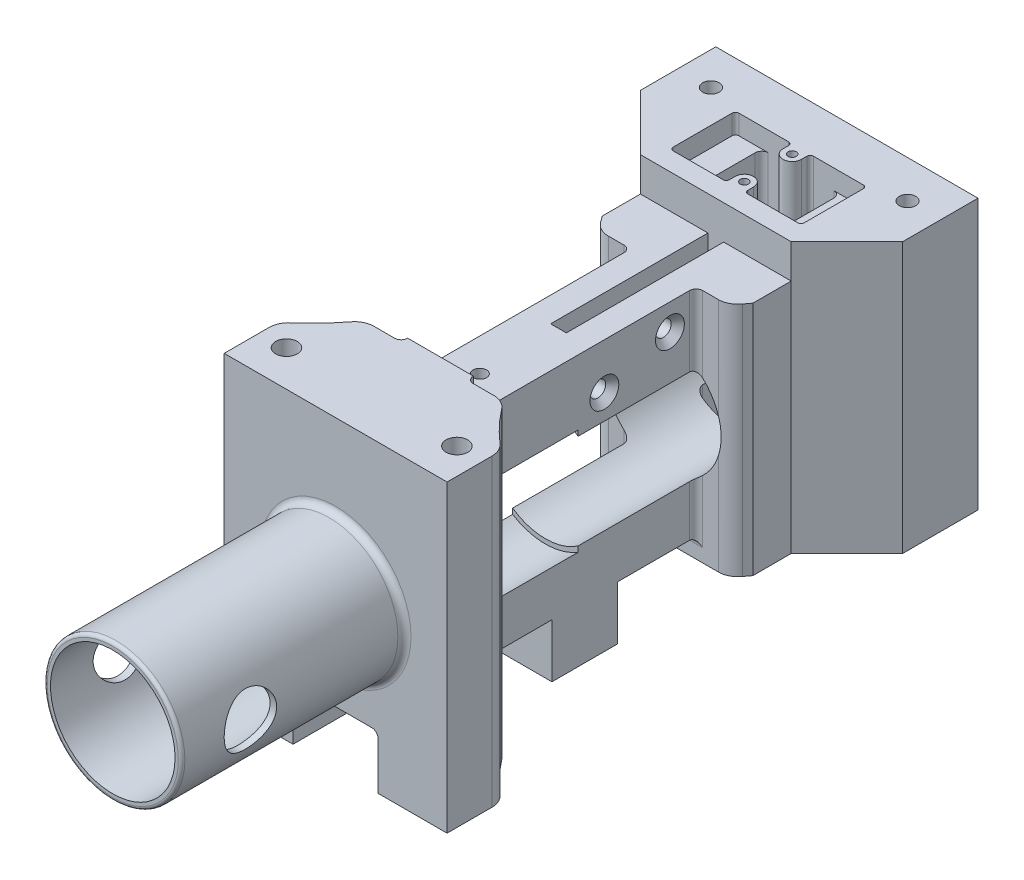
SolidWorks part; units mm, degrees
material "6061 合金"
ref_plane "前视基准面" through (0, 0, 0) normal (0, 0, 1) x (1, 0, 0)
ref_plane "上视基准面" through (0, 0, 0) normal (0, 1, 0) x (1, 0, 0)
ref_plane "右视基准面" through (0, 0, 0) normal (1, 0, 0) x (0, 0, -1)
sketch "草图1" plane through (0, 0, 0) normal (0, 0, 1) x (1, 0, 0)
  line L1 (-20, 18) -> (20, 18)
  line L2 (-20, 18) -> (-20, -18)
  line L3 (-20, -18) -> (20, -18)
  line L4 (20, 18) -> (20, -18)
  line L5 (-20, 18) -> (20, -18) construction
  line L6 (-20, -18) -> (20, 18) construction
  circle A0 centre (0, 0) radius 8.8
  point P0 (0, 0)
  dimension "D1" = 36
  dimension "D3" = 17.6
  dimension "D2" = 40
extrude "凸台-拉伸1" add sketch "草图1" along normal blind 65
sketch "草图2" plane through (0, 0, 0) normal (0, 1, 0) x (1, 0, 0)
  line L0 (0, 0) -> (0, -32) construction
  line L1 (-36.5, -32) -> (36.5, -32) construction
  circle A0 centre (-36.5, -32) radius 31.5
  circle A1 centre (36.5, -32) radius 31.5
  point P6 (0, -32)
  dimension "D1" = 32
  dimension "D3" = 63
  dimension "D2" = 73
extrude "切除-拉伸1" cut sketch "草图2" against normal through all both and the other way through all
ref_plane "基准面1" through (0, 0, 65) normal (0, 0, 1) x (1, 0, 0)
sketch "草图3" plane through (0, 0, 65) normal (0, 0, 1) x (1, 0, 0)
  circle A0 centre (0, 0) radius 9.5
  dimension "D1" = 19
extrude "切除-拉伸2" cut sketch "草图3" against normal blind 32
sketch "草图4" plane through (0, 0, 65) normal (0, 0, 1) x (1, 0, 0)
  circle A0 centre (0, 0) radius 10.5
  circle A1 centre (0, 0) radius 9.5
  dimension "D1" = 19
  dimension "D2" = 21
extrude "凸台-拉伸2" add sketch "草图4" along normal blind 34
sketch "草图5" plane through (0, 0, 0) normal (1, 0, 0) x (0, 0, -1)
  line L0 (0, 0) -> (-65, 0) construction
  line L1 (-65, 19.8) -> (-65, -19.8) construction
  line L2 (-65, 0) -> (-88.5, 0) construction
  circle A0 centre (-88.5, 0) radius 4
  dimension "D2" = 8
  dimension "D1" = 23.5
extrude "切除-拉伸3" cut sketch "草图5" against normal through all both and the other way through all
sketch "草图6" plane through (0, 0, 0) normal (0, 1, 0) x (1, 0, 0)
  line L0 (-1.2, 0) -> (1.2, 0)
  line L1 (20, 0) -> (-20, 0) construction
  line L2 (1.2, 0) -> (1.2, -31)
  line L3 (1.2, -31) -> (-1.2, -31)
  line L4 (-1.2, -31) -> (-1.2, 0)
  point P6 (0, 0)
  dimension "D1" = 2.4
  dimension "D2" = 31
extrude "切除-拉伸4" cut sketch "草图6" along normal through all
sketch "草图7" plane through (0, 0, 0) normal (1, 0, 0) x (0, 0, -1)
  line L0 (0, 0) -> (-44.3363, 0) construction
  line L1 (0, -18) -> (0, 18) construction
  circle A0 centre (-19, 14) radius 0.75
  circle A1 centre (-29, 11) radius 0.75
  dimension "D1" = 14
  dimension "D3" = 1.5
  dimension "D4" = 10
  dimension "D6" = 1.5
  dimension "D2" = 14
  dimension "D5" = 3
extrude "切除-拉伸5" cut sketch "草图7" against normal through all both and the other way through all
fillet "圆角1" radius 1 1 edges at (10.5, 0, 65)
fillet "圆角2" radius 0.5 1 edges at (10.5, 0, 99)
sketch "草图8" plane through (0, 0, 0) normal (0, 0, 1) x (1, 0, 0)
  line L1 (20, -18) -> (-20, -18)
  line L2 (20, -18) -> (20, 18)
  line L3 (20, 18) -> (-20, 18)
  line L4 (-20, -18) -> (-20, 18)
  line L5 (20, -18) -> (-20, 18) construction
  line L6 (20, 18) -> (-20, -18) construction
  point P0 (0, 0)
extrude "切除-拉伸6" cut sketch "草图8" along normal blind 7
ref_plane "基准面2" through (0, -18, 0) normal (0, -1, 0) x (-1, 0, 0)
sketch "草图10" plane through (0, -18, 0) normal (0, -1, 0) x (-1, 0, 0)
  line L0 (-20, -65) -> (20, -65)
  line L1 (20, -65) -> (20, -50)
  line L2 (20, -50) -> (-20, -50)
  line L3 (-20, -50) -> (-20, -65)
  line L4 (-17.3362, -7) -> (17.3362, -7)
  line L5 (17.3362, -7) -> (17.3362, -15)
  line L6 (17.3362, -15) -> (-17.3362, -15)
  line L7 (-17.3362, -15) -> (-17.3362, -7)
  dimension "D1" = 15
  dimension "D2" = 8
extrude "凸台-拉伸3" add sketch "草图10" along normal blind 6.1
sketch "草图17" plane through (0, 0, 0) normal (0, 1, 0) x (1, 0, 0)
  line L0 (0, 0) -> (0, -7) construction
  line L1 (0, -7) -> (-11.5, -7) construction
  line L2 (-11.5, -7) -> (-11.5, -15)
  line L3 (-11.5, -15) -> (-5, -15)
  line L4 (-5, -15) -> (-5, -50)
  line L5 (-5, -50) -> (-17, -50)
  line L6 (-17, -50) -> (-17, -65)
  line L7 (20, -65) -> (-20, -65) construction
  line L8 (-17, -65) -> (-20, -65)
  line L9 (-20, -65) -> (-20, -7)
  line L10 (-20, -7) -> (-11.5, -7)
  line L11 (17, -65) -> (20, -65)
  line L12 (17, -50) -> (17, -65)
  line L13 (5, -50) -> (17, -50)
  line L14 (5, -15) -> (5, -50)
  line L15 (11.5, -15) -> (5, -15)
  line L16 (11.5, -7) -> (11.5, -15)
  line L17 (20, -65) -> (20, -7)
  line L18 (20, -7) -> (11.5, -7)
  dimension "D1" = 7
  dimension "D2" = 11.5
  dimension "D3" = 8
  dimension "D4" = 6.5
  dimension "D5" = 35
  dimension "D6" = 3
extrude "切除-拉伸7" cut sketch "草图17" against normal through all both and the other way through all
sketch "草图20" plane through (0, 0, 0) normal (0, 1, 0) x (1, 0, 0)
  line L0 (0, 0) -> (0, -32) construction
  line L1 (-36.5, -32) -> (36.5, -32) construction
  circle A0 centre (-36.5, -32) radius 31.5
  circle A1 centre (36.5, -32) radius 31.5
  point P6 (0, -32)
  dimension "D1" = 32
  dimension "D3" = 63
  dimension "D2" = 73
extrude "切除-拉伸8" cut sketch "草图20" against normal through all both and the other way through all
sketch "草图21" plane through (0, -18, 0) normal (0, -1, 0) x (-1, 0, 0)
  line L0 (0, -65) -> (-6.5, -65)
  line L1 (-17, -65) -> (17, -65) construction
  line L2 (-6.5, -65) -> (-6.5, -50)
  line L3 (10.6495, -50) -> (-10.6495, -50) construction
  line L4 (-6.5, -50) -> (6.5, -50)
  line L5 (5, -50) -> (-5, -50) construction
  line L6 (6.5, -50) -> (6.5, -65)
  line L7 (6.5, -65) -> (0, -65)
  dimension "D1" = 6.5
  dimension "D2" = 6.5
extrude "切除-拉伸9" cut sketch "草图21" along normal blind 6.1
sketch "草图22" plane through (0, -18, 0) normal (0, -1, 0) x (-1, 0, 0)
  line L0 (-6.5, -65) -> (-6.5, -50)
  line L1 (-6.5, -50) -> (-10.6495, -50)
  line L2 (-10.6495, -50) -> (-10.6495, -15)
  line L5 (0, -65) -> (0, -41.2409) construction
  line L6 (-6.5, -65) -> (6.5, -65) construction
  line L7 (6.5, -65) -> (6.5, -50)
  line L8 (6.5, -50) -> (10.6495, -50)
  line L11 (-6.5, -65) -> (6.5, -65)
  line L12 (10.6495, -50) -> (10.6495, -15)
  line L13 (-10.6495, -15) -> (10.6495, -15)
  point P19 (0, -15)
extrude "切除-拉伸10" cut sketch "草图22" against normal blind 3
ref_plane "基准面3" through (0, 18, 0) normal (0, 1, 0) x (1, 0, 0)
sketch "草图23" plane through (0, 18, 0) normal (0, 1, 0) x (1, 0, 0)
  line L0 (0, -31) -> (0, -43) construction
  line L1 (1.2, -31) -> (-1.2, -31) construction
  dimension "D2" = 12
hole_wizard "M2.5 螺纹孔1" positions "草图24" profile "草图25" tap size "M2.5" standard "ISO"
sketch "草图24" plane through (0, 18, 0) normal (0, 1, 0) x (1, 0, 0)
  point P0 (0, -43)
sketch "草图25" plane through (0, 18, 43) normal (1, 0, 0) x (0, 0, 1)
  line L0 (0, 0) -> (0, 6.6159)
  line L1 (0, 6.6159) -> (1.025, 6)
  line L2 (1.025, 6) -> (1.025, 0)
  line L5 (1.025, 0) -> (0, 0)
  line L10 (0, 6.6159) -> (-1.025, 6) construction
  line L11 (0, -6.35) -> (0, 107.95) construction
  dimension "螺纹孔钻头直径" = 2.05
  dimension "螺纹孔钻头深度" = 6
  dimension "导头角度" = 118
cosmetic thread "孔螺蚊线5" parameters "D1"=5, "D2"=2.5
hole_wizard "M2 十字切槽平头螺钉锥孔1" positions "草图26" profile "草图27" countersink size "M2" standard "IS"
sketch "草图26" plane through (5, 0, 0) normal (1, 0, 0) x (0, 0, -1)
  point P0 (-29, 11)
  point P3 (-19, 14)
sketch "草图27" plane through (5, 11, 29) normal (0, 1, 0) x (0, 0, -1)
  line L0 (0, 0) -> (0, 5.721)
  line L1 (0, 5.721) -> (1.2, 5)
  line L2 (1.2, 5) -> (1.2, 1)
  line L3 (1.2, 1) -> (2.2, 0)
  line L5 (2.2, 0) -> (0, 0)
  line L6 (-1.2, 1) -> (-2.2, 0) construction
  line L10 (0, 5.721) -> (-1.2, 5) construction
  line L11 (0, -6.35) -> (0, 107.95) construction
  dimension "孔直径" = 2.4
  dimension "孔深度" = 5
  dimension "近端锥形沉头孔直径" = 4.4
  dimension "近端锥形沉头孔角度" = 90
  dimension "导头角度" = 118
hole_wizard "M2 螺纹孔2" positions "草图30" profile "草图31" tap size "M2" standard "ISO"
sketch "草图30" plane through (-5, 0, 0) normal (-1, 0, 0) x (0, 0, 1)
  point P0 (19, 14)
  point P3 (29, 11)
sketch "草图31" plane through (-5, 14, 19) normal (0, 1, 0) x (0, 0, 1)
  line L0 (0, 0) -> (0, 6.4807)
  line L1 (0, 6.4807) -> (0.8, 6)
  line L2 (0.8, 6) -> (0.8, 0)
  line L5 (0.8, 0) -> (0, 0)
  line L10 (0, 6.4807) -> (-0.8, 6) construction
  line L11 (0, -6.35) -> (0, 107.95) construction
  dimension "螺纹孔钻头直径" = 1.6
  dimension "螺纹孔钻头深度" = 6
  dimension "导头角度" = 118
cosmetic thread "孔螺蚊线6" parameters "D1"=4, "D2"=2
cosmetic thread "孔螺蚊线7" parameters "D1"=4, "D2"=2
fillet "圆角4" radius 3 6 edges at (9.9811, -3.05, 15) (-9.9811, -3.05, 15) (-10.6495, -3.05, 50) (10.6495, -3.05, 50) (17, -3.05, 56.7386) (-17, -3.05, 56.7386)
fillet "圆角5" radius 1 9 edges at (5, -11.5389, 50) (5, 13.0389, 50) (-5, 13.0389, 50) (-5, -11.5389, 50) (0, -15, 15) (-5, -11.1208, 15) (5, -11.1208, 15) (5, 12.6208, 15) (-5, 12.6208, 15)
fillet "圆角6" radius 1 2 edges at (6.5, -15, 57.5) (-6.5, -15, 57.5)
sketch "草图32" plane through (0, 0, 0) normal (0, 0, 1) x (1, 0, 0)
  line L0 (0, 0) -> (0, -14) construction
  line L1 (6, -14) -> (-6, -14) construction
  line L2 (0, 0) -> (-20.7287, 0) construction
  line L3 (6, 14) -> (-6, 14) construction
  point P6 (0, -14)
  dimension "D1" = 14
  dimension "D2" = 12
sketch "草图35" plane through (0, 18, 0) normal (0, 1, 0) x (1, 0, 0)
  line L5 (-17, -65) -> (17, -65)
  line L6 (17, -65) -> (17, -49)
  line L7 (17, -49) -> (-17, -49)
  line L8 (-17, -49) -> (-17, -65)
  dimension "D1" = 16
extrude "切除-拉伸11" cut sketch "草图35" against normal blind 4
sketch "草图36" plane through (0, -24.1, 0) normal (0, -1, 0) x (1, 0, 0)
  line L0 (44.7398, 127.3141) -> (-24.9416, 127.3141)
  line L1 (-24.9416, 127.3141) -> (-24.9416, -20.2012)
  line L2 (-24.9416, -20.2012) -> (44.7398, -20.2012)
  line L3 (44.7398, -20.2012) -> (44.7398, 127.3141)
extrude "切除-拉伸12" cut sketch "草图36" against normal blind 0.9
sketch "草图37" plane through (0, -23.2, 0) normal (0, -1, 0) x (1, 0, 0)
  line L0 (6.5, 65) -> (17, 65) construction
  line L1 (0, 99) -> (0, 0) construction
  line L2 (10, 99) -> (-10, 99) construction
  circle A0 centre (13, 59.5) radius 1.65
  circle A1 centre (-13, 59.5) radius 1.65
  dimension "D1" = 5.5
  dimension "D2" = 3.3
  dimension "D3" = 13
extrude "切除-拉伸13" cut sketch "草图37" against normal blind 10
cosmetic thread "装饰螺纹线1" parameters "D2"=4
cosmetic thread "装饰螺纹线2" parameters "D2"=4
sketch "草图38" plane through (0, -15, 0) normal (0, -1, 0) x (1, 0, 0)
  line L0 (5, 37) -> (-5, 37)
  line L1 (5, 16) -> (5, 49) construction
  line L2 (-5, 49) -> (-5, 16) construction
  line L3 (-5, 37) -> (-5, 27)
  line L4 (-5, 27) -> (5, 27)
  line L5 (5, 27) -> (5, 37)
  line L6 (-5, 32) -> (5, 32) construction
  line L7 (6.5, 65) -> (17, 65) construction
  dimension "D1" = 33
  dimension "D2" = 10
extrude "凸台-拉伸4" add sketch "草图38" along normal up to surface (8.2 mm away) up to face at (13, -23.2, 57.85)
sketch "草图39" plane through (0, -23.2, 0) normal (0, -1, 0) x (1, 0, 0)
  line L0 (5, 27) -> (5, 37) construction
  line L1 (5, 37) -> (-5, 37) construction
  circle A0 centre (0, 32) radius 1.65
  dimension "D1" = 5
  dimension "D3" = 3.3
  dimension "D2" = 5
extrude "切除-拉伸14" cut sketch "草图39" against normal blind 8
cosmetic thread "装饰螺纹线3" parameters "D2"=4
sketch "草图42" plane through (0, 14, 0) normal (0, 1, 0) x (1, 0, 0)
  line L6 (9.1276, -50) -> (6, -50)
  line L7 (5, -49) -> (-5, -49)
  line L8 (9.1276, -50) -> (6, -50)
  line L9 (-17, -58.1534) -> (-17, -65)
  line L10 (-17, -65) -> (17, -65)
  line L11 (17, -65) -> (17, -58.1534)
  line L13 (5, -49) -> (-5, -49)
  line L15 (-17, -58.1534) -> (-17, -65)
  line L16 (-17, -65) -> (17, -65)
  line L17 (17, -65) -> (17, -58.1534)
  line L18 (-6, -50) -> (-9.1276, -50)
  line L19 (-6, -50) -> (-9.1276, -50)
  arc A8 (11.5078, -51.1739) -> (15.9565, -55.8792) centre (36.5, -32) ccw
  arc A9 (11.5078, -51.1739) -> (9.1276, -50) centre (9.1276, -53) ccw
  arc A10 (11.5078, -51.1739) -> (9.1276, -50) centre (9.1276, -53) ccw
  arc A11 (5, -49) -> (6, -50) centre (6, -49) ccw
  arc A12 (5, -49) -> (6, -50) centre (6, -49) ccw
  arc A13 (-15.9565, -55.8792) -> (-11.5078, -51.1739) centre (-36.5, -32) ccw
  arc A14 (-15.9565, -55.8792) -> (-17, -58.1534) centre (-14, -58.1534) ccw
  arc A15 (17, -58.1534) -> (15.9565, -55.8792) centre (14, -58.1534) ccw
  arc A16 (11.5078, -51.1739) -> (15.9565, -55.8792) centre (36.5, -32) ccw
  arc A21 (-15.9565, -55.8792) -> (-11.5078, -51.1739) centre (-36.5, -32) ccw
  arc A22 (-15.9565, -55.8792) -> (-17, -58.1534) centre (-14, -58.1534) ccw
  arc A23 (17, -58.1534) -> (15.9565, -55.8792) centre (14, -58.1534) ccw
  arc A24 (-6, -50) -> (-5, -49) centre (-6, -49) ccw
  arc A25 (-6, -50) -> (-5, -49) centre (-6, -49) ccw
  arc A26 (-9.1276, -50) -> (-11.5078, -51.1739) centre (-9.1276, -53) ccw
  arc A27 (-9.1276, -50) -> (-11.5078, -51.1739) centre (-9.1276, -53) ccw
  dimension "D1" = 0
sketch "草图44" plane through (0, 18, 0) normal (0, 1, 0) x (1, 0, 0)
  line L0 (0, 0) -> (0, -37.7953) construction
  line L1 (-11.5, -7) -> (-20, 1.5)
  line L2 (-20, 1.5) -> (-20, 13)
  line L3 (-20, 13) -> (20, 13)
  line L4 (-11.5, -7) -> (11.5, -7)
  line L5 (20, 1.5) -> (20, 13)
  line L6 (11.5, -7) -> (20, 1.5)
  point P10 (0, -7)
  point P11 (0, 13)
  dimension "D1" = 20
  dimension "D2" = 45
  dimension "D3" = 20
extrude "凸台-拉伸7" add sketch "草图44" against normal offset from surface (36 mm away) 3 up to face at (0, -15, 21.5) offset beyond the face yes
sketch "草图46" plane through (0, 0, 7) normal (0, 0, 1) x (1, 0, 0)
  circle A0 centre (0, 0) radius 8.8
  dimension "D1" = 17.6
extrude "切除-拉伸17" cut sketch "草图46" against normal through all
sketch "草图47" plane through (0, 0, -13) normal (0, 0, -1) x (-1, 0, 0)
  line L0 (0, 0) -> (0, 24.5085) construction
  line L1 (0, 0) -> (35.6135, 0) construction
  circle A0 centre (13, 13) radius 1.25
  circle A1 centre (-13, 13) radius 1.25
  circle A2 centre (-13, -13) radius 1.25
  circle A3 centre (13, -13) radius 1.25
  dimension "D1" = 2.5
  dimension "D2" = 13
  dimension "D3" = 13
extrude "切除-拉伸18" cut sketch "草图47" against normal blind 6
cosmetic thread "装饰螺纹线8" parameters "D2"=3
cosmetic thread "装饰螺纹线9" parameters "D2"=3
cosmetic thread "装饰螺纹线10" parameters "D2"=3
cosmetic thread "装饰螺纹线11" parameters "D2"=3
cosmetic thread "装饰螺纹线16" parameters "D2"=3
cosmetic thread "装饰螺纹线17" parameters "D2"=3
cosmetic thread "装饰螺纹线18" parameters "D2"=3
cosmetic thread "装饰螺纹线19" parameters "D2"=3
sketch "草图48" plane through (0, 18, 0) normal (0, 1, 0) x (1, 0, 0)
  line L1 (20, 1.5) -> (20, 13) construction
  line L2 (-20, 13) -> (-20, 1.5) construction
  line L3 (20, 13) -> (-20, 13) construction
  line L4 (-20, 13) -> (-20, 1.5)
  line L5 (20, 13) -> (-20, 13)
  line L6 (20, 1.5) -> (20, 13)
  line L7 (11.5, -7) -> (20, 1.5) construction
  line L8 (-20, 1.5) -> (-11.5, -7) construction
  line L9 (11.5, -7) -> (20, 1.5)
  line L10 (-20, 1.5) -> (-11.5, -7)
  line L11 (-11.5, -7) -> (11.5, -7)
extrude "凸台-拉伸8" add sketch "草图48" along normal blind 5.2
sketch "草图49" plane through (0, 23.2, 0) normal (0, 1, 0) x (1, 0, 0)
  line L0 (20, 7.25) -> (-20, 7.25) construction
  line L1 (20, 1.5) -> (20, 13) construction
  line L2 (-20, 13) -> (-20, 1.5) construction
  circle A0 centre (15, 7.25) radius 1.25
  circle A1 centre (-15, 7.25) radius 1.25
  dimension "D1" = 2.5
  dimension "D2" = 2.5
  dimension "D4" = 5
  dimension "D3" = 5
extrude "切除-拉伸19" cut sketch "草图49" against normal blind 5
cosmetic thread "装饰螺纹线12" parameters "D2"=3
cosmetic thread "装饰螺纹线13" parameters "D2"=3
sketch "草图50" plane through (0, 14, 0) normal (0, 1, 0) x (1, 0, 0)
  line L6 (9.1276, -50) -> (6, -50)
  line L7 (5, -49) -> (-5, -49)
  line L8 (-6, -50) -> (-9.1276, -50)
  line L9 (-17, -58.1534) -> (-17, -65)
  line L10 (-17, -65) -> (17, -65)
  line L11 (17, -65) -> (17, -58.1534)
  line L12 (9.1276, -50) -> (6, -50)
  line L13 (5, -49) -> (-5, -49)
  line L14 (-6, -50) -> (-9.1276, -50)
  line L15 (-17, -58.1534) -> (-17, -65)
  line L16 (-17, -65) -> (17, -65)
  line L17 (17, -65) -> (17, -58.1534)
  arc A8 (11.5078, -51.1739) -> (15.9565, -55.8792) centre (36.5, -32) ccw
  arc A9 (11.5078, -51.1739) -> (9.1276, -50) centre (9.1276, -53) ccw
  arc A10 (5, -49) -> (6, -50) centre (6, -49) ccw
  arc A11 (-6, -50) -> (-5, -49) centre (-6, -49) ccw
  arc A12 (-9.1276, -50) -> (-11.5078, -51.1739) centre (-9.1276, -53) ccw
  arc A13 (-15.9565, -55.8792) -> (-11.5078, -51.1739) centre (-36.5, -32) ccw
  arc A14 (-15.9565, -55.8792) -> (-17, -58.1534) centre (-14, -58.1534) ccw
  arc A15 (17, -58.1534) -> (15.9565, -55.8792) centre (14, -58.1534) ccw
  arc A16 (11.5078, -51.1739) -> (15.9565, -55.8792) centre (36.5, -32) ccw
  arc A17 (11.5078, -51.1739) -> (9.1276, -50) centre (9.1276, -53) ccw
  arc A18 (5, -49) -> (6, -50) centre (6, -49) ccw
  arc A19 (-6, -50) -> (-5, -49) centre (-6, -49) ccw
  arc A20 (-9.1276, -50) -> (-11.5078, -51.1739) centre (-9.1276, -53) ccw
  arc A21 (-15.9565, -55.8792) -> (-11.5078, -51.1739) centre (-36.5, -32) ccw
  arc A22 (-15.9565, -55.8792) -> (-17, -58.1534) centre (-14, -58.1534) ccw
  arc A23 (17, -58.1534) -> (15.9565, -55.8792) centre (14, -58.1534) ccw
  dimension "D1" = 0
extrude "凸台-拉伸9" add sketch "草图50" along normal up to surface (9.2 mm away) up to face at (15, 23.2, -6)
sketch "草图51" plane through (0, 23.2, 0) normal (0, 1, 0) x (1, 0, 0)
  circle A0 centre (-13, -59.5) radius 1.65 construction
  circle A1 centre (13, -59.5) radius 1.65 construction
  circle A2 centre (-13, -59.5) radius 1.65
  circle A3 centre (13, -59.5) radius 1.65
extrude "切除-拉伸20" cut sketch "草图51" against normal blind 10
cosmetic thread "装饰螺纹线14" parameters "D2"=4
cosmetic thread "装饰螺纹线15" parameters "D2"=4
sketch "草图52" plane through (0, 23.2, 0) normal (0, 1, 0) x (1, 0, 0)
  line L0 (-6, -4) -> (-1.4, -4)
  line L1 (6, -4) -> (6, 6)
  line L2 (6, 6) -> (1.4, 6)
  line L3 (-6, 6) -> (-6, -4)
  line L4 (0, 0) -> (0, 19.8256) construction
  line L5 (-6, 1) -> (6, 1) construction
  line L6 (-1.4, 4.65) -> (-1.4, 6)
  line L7 (1.4, 4.65) -> (1.4, 6)
  line L8 (-1.4, 6) -> (-6, 6)
  line L9 (-1.4, -2.65) -> (-1.4, -4)
  line L10 (1.4, -2.65) -> (1.4, -4)
  line L11 (1.4, -4) -> (6, -4)
  arc A0 (-1.4, 4.65) -> (1.4, 4.65) centre (0, 4.65) ccw
  arc A1 (-1.4, -2.65) -> (1.4, -2.65) centre (0, -2.65) cw
  dimension "D5" = 2.8
  dimension "D1" = 6
  dimension "D2" = 6
  dimension "D3" = 4
  dimension "D4" = 6
  dimension "D6" = 7.3
extrude "切除-拉伸21" cut sketch "草图52" against normal through all
sketch "草图53" plane through (0, 23.2, 0) normal (0, 1, 0) x (1, 0, 0)
  line L0 (-1.4, 6) -> (-6, 6) construction
  line L1 (10, 6) -> (1.4, 6)
  line L2 (-6, -4) -> (-1.4, -4) construction
  line L3 (-10, -4) -> (-1.4, -4)
  line L4 (-10, 6) -> (-10, -4)
  line L5 (10, 6) -> (10, -4)
  line L6 (1.4, -2.65) -> (1.4, -4) construction
  line L7 (-1.4, -4) -> (-1.4, -2.65) construction
  line L8 (1.4, 6) -> (1.4, 4.65) construction
  line L9 (-1.4, 4.65) -> (-1.4, 6) construction
  line L10 (1.4, -2.65) -> (1.4, -4)
  line L11 (-1.4, -4) -> (-1.4, -2.65)
  line L12 (1.4, 6) -> (1.4, 4.65)
  line L13 (-1.4, 4.65) -> (-1.4, 6)
  line L14 (-1.4, 6) -> (-10, 6)
  line L15 (1.4, -4) -> (10, -4)
  arc A0 (1.4, -2.65) -> (-1.4, -2.65) centre (0, -2.65) ccw construction
  arc A1 (-1.4, 4.65) -> (1.4, 4.65) centre (0, 4.65) ccw construction
  arc A2 (1.4, -2.65) -> (-1.4, -2.65) centre (0, -2.65) ccw
  arc A3 (-1.4, 4.65) -> (1.4, 4.65) centre (0, 4.65) ccw
  dimension "D1" = 10
  dimension "D2" = 10
extrude "切除-拉伸22" cut sketch "草图53" against normal blind 3
sketch "草图54" plane through (0, -18, 0) normal (0, -1, 0) x (1, 0, 0)
  line L10 (1.4, -4.65) -> (1.4, -6)
  line L11 (-1.4, -6) -> (-1.4, -4.65)
  line L12 (-10, -6) -> (-1.4, -6)
  line L13 (-10, 4) -> (-10, -6)
  line L14 (-1.4, 4) -> (-10, 4)
  line L15 (-1.4, 2.65) -> (-1.4, 4)
  line L16 (1.4, 4) -> (1.4, 2.65)
  line L17 (10, 4) -> (1.4, 4)
  line L18 (10, -6) -> (10, 4)
  line L19 (1.4, -6) -> (10, -6)
  line L20 (1.4, -4.65) -> (1.4, -6)
  line L21 (-1.4, -6) -> (-1.4, -4.65)
  line L22 (-10, -6) -> (-1.4, -6)
  line L23 (-10, 4) -> (-10, -6)
  line L24 (-1.4, 4) -> (-10, 4)
  line L25 (-1.4, 2.65) -> (-1.4, 4)
  line L26 (1.4, 4) -> (1.4, 2.65)
  line L27 (10, 4) -> (1.4, 4)
  line L28 (10, -6) -> (10, 4)
  line L29 (1.4, -6) -> (10, -6)
  arc A2 (1.4, -4.65) -> (-1.4, -4.65) centre (0, -4.65) ccw
  arc A3 (-1.4, 2.65) -> (1.4, 2.65) centre (0, 2.65) ccw
  arc A4 (1.4, -4.65) -> (-1.4, -4.65) centre (0, -4.65) ccw
  arc A5 (-1.4, 2.65) -> (1.4, 2.65) centre (0, 2.65) ccw
  dimension "D1" = 0
extrude "切除-拉伸23" cut sketch "草图54" against normal blind 3
sketch "草图55" plane through (0, 23.2, 0) normal (0, 1, 0) x (1, 0, 0)
  circle A0 centre (0, -2.65) radius 0.625
  circle A1 centre (0, 4.65) radius 0.625
  dimension "D1" = 1.25
  dimension "D2" = 1.25
extrude "切除-拉伸24" cut sketch "草图55" against normal blind 5
cosmetic thread "装饰螺纹线22" parameters "D2"=1.6
cosmetic thread "装饰螺纹线23" parameters "D2"=1.6
sketch "草图56" plane through (0, -18, 0) normal (0, -1, 0) x (1, 0, 0)
  circle A1 centre (0, -4.65) radius 0.625
  circle A2 centre (0, -4.65) radius 0.625
  circle A3 centre (0, 2.65) radius 0.625
  circle A4 centre (0, 2.65) radius 0.625
  dimension "D1" = 0
  dimension "D2" = 0
extrude "切除-拉伸25" cut sketch "草图56" against normal blind 5
cosmetic thread "装饰螺纹线20" parameters "D2"=1.6
cosmetic thread "装饰螺纹线21" parameters "D2"=1.6
fillet "圆角7" radius 0.5 8 edges at (-1.4, 15.944, -6) (1.4, 15.944, -6) (1.4, 15.944, 4) (-1.4, 15.944, 4) (-10, 21.7, 4) (-10, 21.7, -6) (10, 21.7, -6) (10, 21.7, 4)
fillet "圆角8" radius 1 4 edges at (-6, 13.3187, -6) (6, 13.3187, -6) (6, 13.3187, 4) (-6, 13.3187, 4)
fillet "圆角9" radius 1 4 edges at (6, -10.7187, 4) (6, -10.7187, -6) (-6, -10.7187, -6) (-6, -10.7187, 4)
fillet "圆角10" radius 0.5 8 edges at (1.4, -13.344, 4) (-1.4, -13.344, 4) (-1.4, -13.344, -6) (1.4, -13.344, -6) (10, -16.5, -6) (10, -16.5, 4) (-10, -16.5, -6) (-10, -16.5, 4)
sketch "草图57" plane through (0, -23.2, 0) normal (0, -1, 0) x (1, 0, 0)
  line L4 (11.5, 7) -> (11.5, 12.8362)
  line L5 (8.3886, 15) -> (-8.3886, 15)
  line L6 (-11.5, 12.8362) -> (-11.5, 7)
  line L7 (-11.5, 7) -> (11.5, 7)
  line L8 (11.5, 7) -> (11.5, 12.8362)
  line L9 (8.3886, 15) -> (-8.3886, 15)
  line L10 (-11.5, 12.8362) -> (-11.5, 7)
  line L11 (-11.5, 7) -> (11.5, 7)
  arc A4 (10.8331, 13.7391) -> (11.5, 12.8362) centre (36.5, 32) ccw
  arc A5 (10.8331, 13.7391) -> (8.3886, 15) centre (8.3886, 12) ccw
  arc A6 (-8.3886, 15) -> (-10.8331, 13.7391) centre (-8.3886, 12) ccw
  arc A7 (-11.5, 12.8362) -> (-10.8331, 13.7391) centre (-36.5, 32) ccw
  arc A8 (10.8331, 13.7391) -> (11.5, 12.8362) centre (36.5, 32) ccw
  arc A9 (10.8331, 13.7391) -> (8.3886, 15) centre (8.3886, 12) ccw
  arc A10 (-8.3886, 15) -> (-10.8331, 13.7391) centre (-8.3886, 12) ccw
  arc A11 (-11.5, 12.8362) -> (-10.8331, 13.7391) centre (-36.5, 32) ccw
  dimension "D1" = 0
extrude "切除-拉伸26" cut sketch "草图57" against normal up to surface (5.2 mm away) up to face at (0, -18, -5.275)
